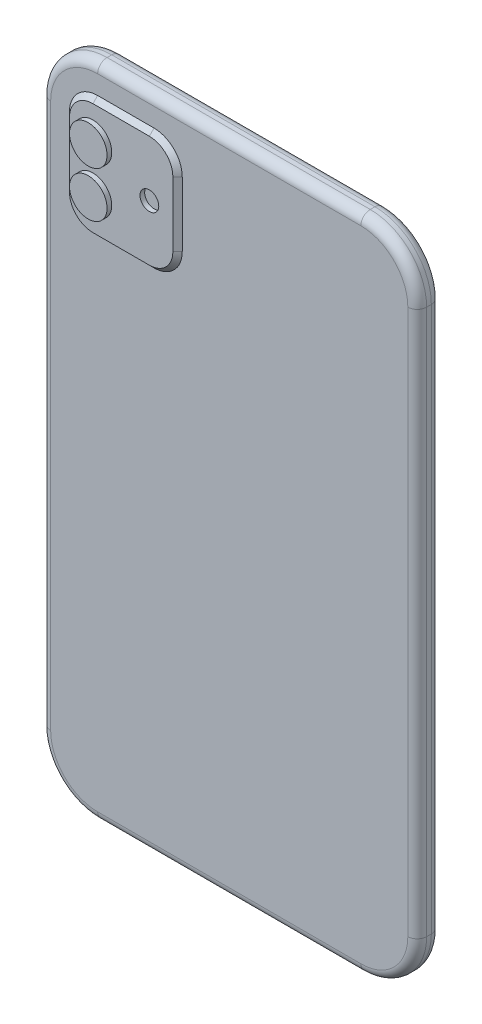
SolidWorks part; units mm, degrees
ref_plane "Front Plane" through (0, 0, 0) normal (0, 0, 1) x (1, 0, 0)
ref_plane "Top Plane" through (0, 0, 0) normal (0, 1, 0) x (1, 0, 0)
ref_plane "Right Plane" through (0, 0, 0) normal (1, 0, 0) x (0, 0, -1)
sketch "Sketch1" plane through (0, 0, 0) normal (0, 0, 1) x (1, 0, 0)
  line L1 (-50.8, -88.9) -> (50.8, -88.9)
  line L2 (-50.8, -88.9) -> (-50.8, 88.9)
  line L3 (-50.8, 88.9) -> (50.8, 88.9)
  line L4 (50.8, -88.9) -> (50.8, 88.9)
  line L5 (-50.8, -88.9) -> (50.8, 88.9) construction
  line L6 (-50.8, 88.9) -> (50.8, -88.9) construction
  point P0 (0, 0)
extrude "Boss-Extrude2" add sketch "Sketch1" along normal blind 6.35
fillet "Fillet1" radius 15.24 4 edges at (-50.8, -88.9, 3.175) (50.8, -88.9, 3.175) (50.8, 88.9, 3.175) (-50.8, 88.9, 3.175)
sketch "Sketch2" plane through (0, 0, 0) normal (0, 0, 1) x (1, 0, 0)
  line L13 (12.7, 76.2) -> (-12.7, 76.2)
  line L16 (17.78, 81.28) -> (17.78, 86.36)
  line L17 (17.78, 86.36) -> (35.56, 86.36)
  line L20 (48.26, 73.66) -> (48.26, -73.66)
  line L21 (35.56, -86.36) -> (-35.56, -86.36)
  line L22 (-48.26, -73.66) -> (-48.26, 73.66)
  line L26 (-17.78, 81.28) -> (-17.78, 86.36)
  line L27 (-17.78, 86.36) -> (-35.56, 86.36)
  arc A0 (17.78, 81.28) -> (12.7, 76.2) centre (12.7, 81.28) cw
  arc A1 (35.56, 86.36) -> (48.26, 73.66) centre (35.56, 73.66) cw
  arc A2 (48.26, -73.66) -> (35.56, -86.36) centre (35.56, -73.66) cw
  arc A3 (-35.56, -86.36) -> (-48.26, -73.66) centre (-35.56, -73.66) cw
  arc A4 (-48.26, 73.66) -> (-35.56, 86.36) centre (-35.56, 73.66) cw
  arc A5 (-12.7, 76.2) -> (-17.78, 81.28) centre (-12.7, 81.28) cw
extrude "Boss-Extrude5" add sketch "Sketch2" against normal blind 0.508
sketch "Sketch3" plane through (0, 0, 0) normal (0, 0, 1) x (1, 0, 0)
  line L5 (5.08, 82.5352) -> (-5.08, 82.5352) construction
  line L6 (5.08, 81.2652) -> (-5.08, 81.2652)
  line L7 (5.08, 83.8052) -> (-5.08, 83.8052)
  arc A0 (5.08, 81.2652) -> (5.08, 83.8052) centre (5.08, 82.5352) ccw
  arc A1 (-5.08, 83.8052) -> (-5.08, 81.2652) centre (-5.08, 82.5352) ccw
  point P5 (0, 82.5352)
extrude "Cut-Extrude1" cut sketch "Sketch3" along normal blind 0.254
fillet "Fillet3" radius 2.54 8 edges at (0, 88.9, 0) (-46.3363, 84.4363, 0) (-50.8, 0, 0) (-46.3363, -84.4363, 0) (0, -88.9, 0) (46.3363, -84.4363, 0) (50.8, 0, 0) (46.3363, 84.4363, 0)
fillet "Fillet4" radius 2.54 8 edges at (46.3363, -84.4363, 6.35) (0, -88.9, 6.35) (-46.3363, -84.4363, 6.35) (-50.8, 0, 6.35) (-46.3363, 84.4363, 6.35) (0, 88.9, 6.35) (46.3363, 84.4363, 6.35) (50.8, 0, 6.35)
ref_plane "Plane1" through (0, 0, 6.35) normal (0, 0, 1) x (1, 0, 0)
sketch "Sketch4" plane through (0, 0, 6.35) normal (0, 0, 1) x (1, 0, 0)
  line L5 (-12.7, 73.66) -> (-12.7, 56.1734)
  line L6 (-43.18, 73.66) -> (-43.18, 56.1734)
  line L9 (-35.56, 81.28) -> (-20.32, 81.28)
  line L10 (-35.56, 48.5534) -> (-20.32, 48.5534)
  arc A0 (-43.18, 73.66) -> (-35.56, 81.28) centre (-35.56, 73.66) cw
  arc A1 (-20.32, 81.28) -> (-12.7, 73.66) centre (-20.32, 73.66) cw
  arc A2 (-35.56, 48.5534) -> (-43.18, 56.1734) centre (-35.56, 56.1734) cw
  arc A3 (-12.7, 56.1734) -> (-20.32, 48.5534) centre (-20.32, 56.1734) cw
extrude "Boss-Extrude7" add sketch "Sketch4" along normal blind 1.27
ref_plane "Plane2" through (0, 0, 7.62) normal (0, 0, 1) x (1, 0, 0)
sketch "Sketch6" plane through (0, 0, 7.62) normal (0, 0, 1) x (1, 0, 0)
  circle A0 centre (-35.56, 58.7134) radius 5.08
  circle A1 centre (-35.56, 71.12) radius 5.08
extrude "Boss-Extrude10" add sketch "Sketch6" along normal blind 1.27
sketch "Sketch7" plane through (0, 0, 7.62) normal (0, 0, 1) x (1, 0, 0)
  circle A0 centre (-20.32, 64.9167) radius 2.54
extrude "Cut-Extrude2" cut sketch "Sketch7" against normal blind 1.27
chamfer "Chamfer1" distance 1.27 angle 45 8 edges at (-27.94, 81.28, 7.62) (-14.9318, 79.0482, 7.62) (-12.7, 64.9167, 7.62) (-14.9318, 50.7853, 7.62) (-27.94, 48.5534, 7.62) (-40.9482, 50.7853, 7.62) (-43.18, 64.9167, 7.62) (-40.9482, 79.0482, 7.62)
ref_plane "Plane3" through (0, -88.9, 0) normal (0, 1, 0) x (1, 0, 0)
sketch "Sketch9" plane through (0, -88.9, 0) normal (0, 1, 0) x (1, 0, 0)
  line L2 (5.0172, -3.175) -> (-5.0172, -3.175) construction
  line L4 (5.0172, -3.7621) -> (-5.0172, -3.7621)
  line L5 (5.0172, -2.5879) -> (-5.0172, -2.5879)
  arc A0 (5.0172, -3.7621) -> (5.0172, -2.5879) centre (5.0172, -3.175) ccw
  arc A1 (-5.0172, -2.5879) -> (-5.0172, -3.7621) centre (-5.0172, -3.175) ccw
  point P7 (0, -3.175)
extrude "Cut-Extrude6" cut sketch "Sketch9" along normal blind 6.35
